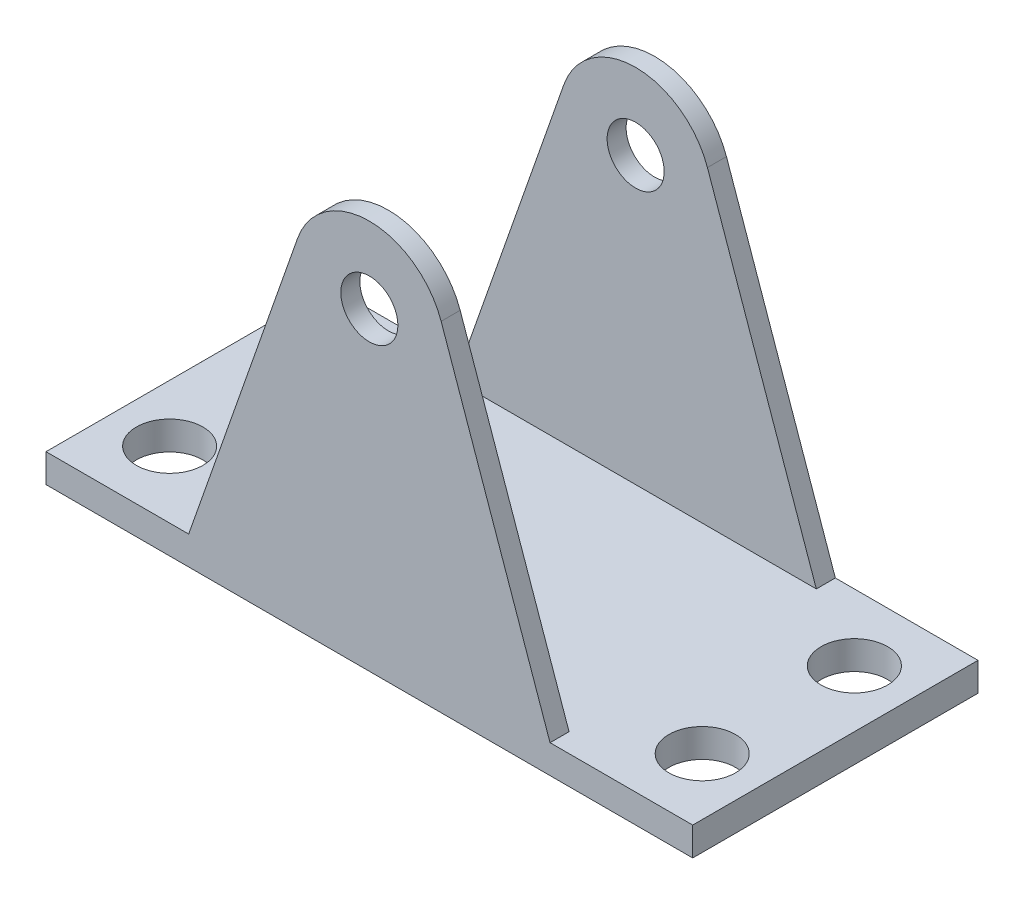
SolidWorks part; units mm, degrees
material "镀铬不锈钢"
ref_plane "前视基准面" through (0, 0, 0) normal (0, 0, 1) x (1, 0, 0)
ref_plane "上视基准面" through (0, 0, 0) normal (0, 1, 0) x (1, 0, 0)
ref_plane "右视基准面" through (0, 0, 0) normal (1, 0, 0) x (0, 0, -1)
other "Configuration Table"
sketch "草图1" plane through (0, 0, 0) normal (0, 1, 0) x (1, 0, 0)
  line L1 (0, 0) -> (68, 0)
  line L2 (0, 0) -> (0, 30)
  line L3 (0, 30) -> (68, 30)
  line L4 (68, 0) -> (68, 30)
  dimension "D1" = 68
  dimension "D2" = 30
extrude "凸台-拉伸1" add sketch "草图1" along normal blind 3
sketch "草图2" plane through (0, 0, 0) normal (0, 0, 1) x (1, 0, 0)
  line L0 (15, 3) -> (26.4509, 35.6478)
  line L1 (0, 3) -> (68, 3) construction
  line L2 (41.5491, 35.6478) -> (53, 3)
  line L3 (53, 3) -> (68, 3) construction
  line L4 (15, 3) -> (0, 3) construction
  line L5 (26.4509, 35.6478) -> (41.5491, 35.6478) construction
  line L6 (0, 0) -> (68, 0) construction
  line L7 (15, 3) -> (53, 3)
  arc A0 (26.4509, 35.6478) -> (41.5491, 35.6478) centre (34, 33) cw
  circle A1 centre (34, 33) radius 3
  dimension "D2" = 8
  dimension "D4" = 6
  dimension "D1" = 33
  dimension "D3" = 15
extrude "凸台-拉伸2" add sketch "草图2" against normal blind 2
extrude "凸台-拉伸3" add sketch "草图2<2>" along normal blind 2 from surface starting at face at (34, 1.5, -30)
sketch "草图2<2>" plane through (0, 0, 0) normal (0, 0, 1) x (1, 0, 0) same geometry as "草图2"
sketch "草图3" plane through (0, 0, 0) normal (0, -1, 0) x (1, 0, 0)
  line L0 (62, -7) -> (6, -7) construction
  line L1 (6, -7) -> (6, -23) construction
  line L2 (6, -23) -> (62, -23) construction
  line L3 (62, -23) -> (62, -7) construction
  line L4 (68, 0) -> (68, -30) construction
  line L6 (68, -30) -> (0, -30) construction
  circle A0 centre (6, -7) radius 3.5
  circle A1 centre (6, -23) radius 3.5
  circle A2 centre (62, -7) radius 3.5
  circle A3 centre (62, -23) radius 3.5
  point P9 (62, -15)
  dimension "D1" = 7
  dimension "D2" = 16
  dimension "D3" = 56
  dimension "D4" = 6
  dimension "D5" = 7
extrude "切除-拉伸1" cut sketch "草图3" against normal blind 12
